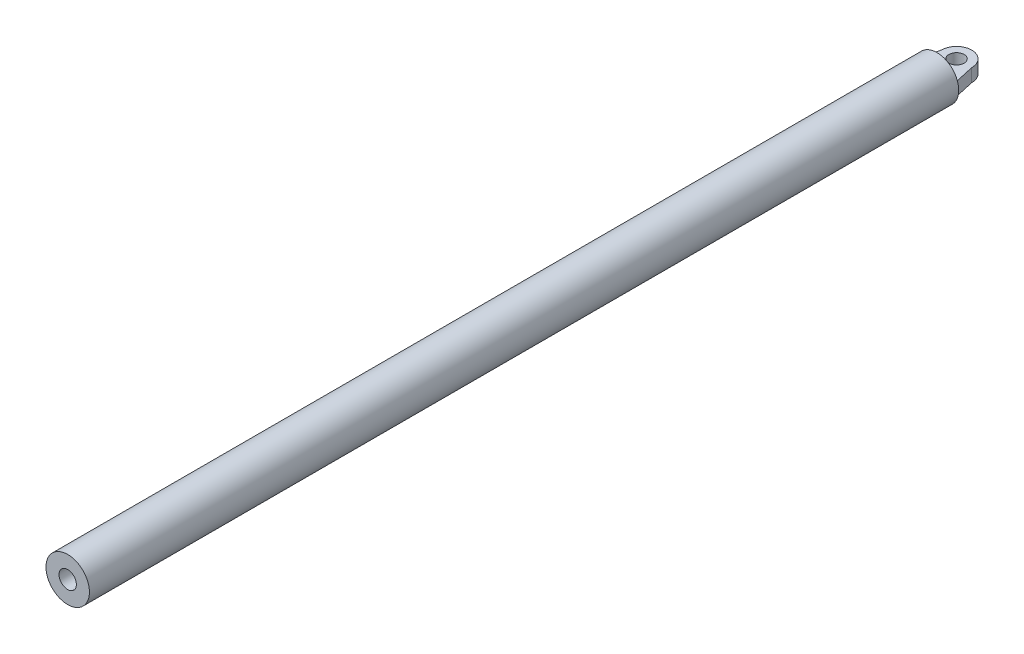
SolidWorks part; units mm, degrees
ref_plane "Front Plane" through (0, 0, 0) normal (0, 0, 1) x (1, 0, 0)
ref_plane "Top Plane" through (0, 0, 0) normal (0, 1, 0) x (1, 0, 0)
ref_plane "Right Plane" through (0, 0, 0) normal (1, 0, 0) x (0, 0, -1)
sketch "Sketch1" plane through (0, 0, 0) normal (0, 0, 1) x (1, 0, 0)
  circle A0 centre (0, 0) radius 50
  dimension "D1" = 100
extrude "Boss-Extrude1" add sketch "Sketch1" along normal blind 2000
sketch "Sketch3" plane through (0, 0, 0) normal (0, 1, 0) x (1, 0, 0)
  line L0 (50, 0) -> (-50, 0) construction
  line L1 (-45, 0) -> (45, 0)
  line L2 (-45, 0) -> (-35, 45)
  line L3 (-35, 45) -> (-35.0741, 45.3303)
  line L4 (35, 45) -> (45, 0)
  line L5 (45, 0) -> (44.7988, -0.1795)
  circle A0 centre (0, 45) radius 17.5
  arc A1 (-35, 45) -> (35, 45) centre (0, 45) cw
  point P5 (-45, 0)
  point P9 (45, 0)
  dimension "D1" = 35
  dimension "D3" = 45
  dimension "D5" = 35
  dimension "D2" = 45
  dimension "D4" = 45
extrude "Boss-Extrude2" add sketch "Sketch3" along normal mid plane 30 contours A1 L2 L1 L4 A0 region at (-38.8245, 0, -22.2388)
shell "Shell1" thickness 30 removed face at (50, 0, 2000)
